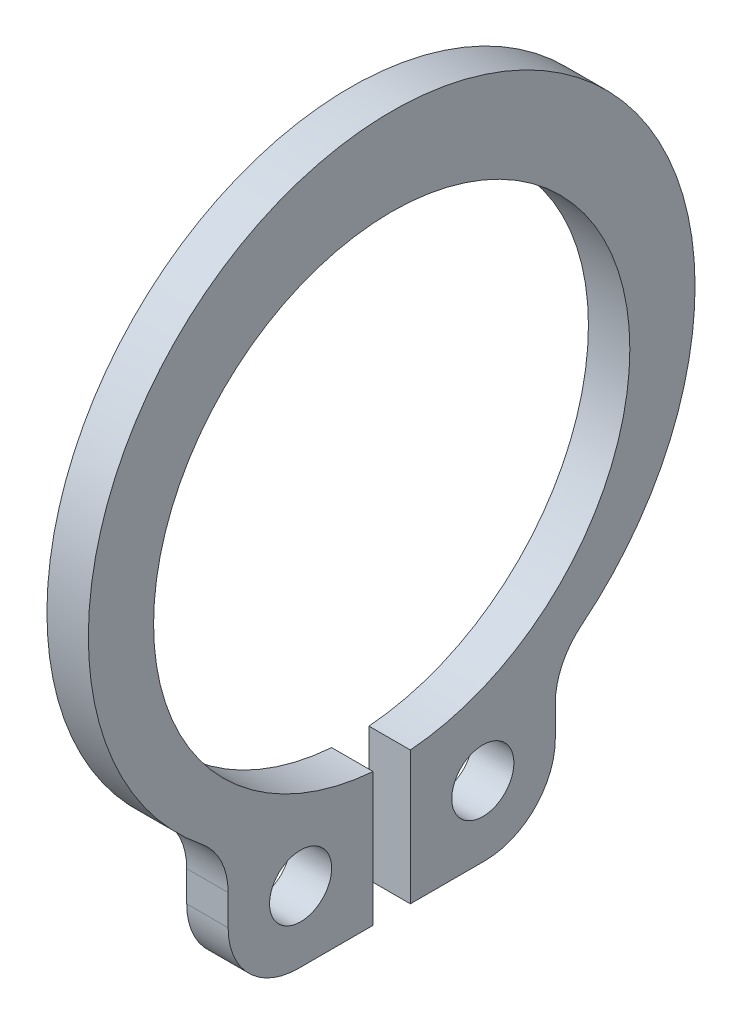
SolidWorks part; units mm, degrees
ref_plane "正面" through (0, 0, 0) normal (0, 0, 1) x (1, 0, 0)
ref_plane "平面" through (0, 0, 0) normal (0, 1, 0) x (1, 0, 0)
ref_plane "右側面" through (0, 0, 0) normal (1, 0, 0) x (0, 0, -1)
ref_plane "平面1" through (0, 0, 0) normal (1, 0, 0) x (0, 0, -1)
sketch "ｽｹｯﾁ1" plane through (0, 0, 0) normal (1, 0, 0) x (0, 0, -1)
  line L0 (-3.95, -6.5126) -> (-3.95, -7.25)
  line L1 (-2.25, -8.95) -> (-0.45, -8.95)
  line L2 (-0.45, -8.95) -> (-0.45, -5.7324)
  line L3 (0.45, -5.7324) -> (0.45, -8.95)
  line L4 (0.45, -8.95) -> (2.25, -8.95)
  line L5 (3.95, -7.25) -> (3.95, -6.5126)
  arc A0 (4.5857, -5.187) -> (-4.5857, -5.187) centre (0, 0.525) ccw
  arc A1 (-4.5857, -5.187) -> (-3.95, -6.5126) centre (-5.65, -6.5126) cw
  arc A2 (-3.95, -7.25) -> (-2.25, -8.95) centre (-2.25, -7.25) ccw
  arc A3 (-0.45, -5.7324) -> (0.45, -5.7324) centre (0, 0) cw
  arc A4 (2.25, -8.95) -> (3.95, -7.25) centre (2.25, -7.25) ccw
  arc A5 (3.95, -6.5126) -> (4.5857, -5.187) centre (5.65, -6.5126) cw
  circle A6 centre (2.2, -7.25) radius 0.75
  circle A7 centre (-2.2, -7.25) radius 0.75
extrude "ﾎﾞｽ - 押し出し1" add sketch "ｽｹｯﾁ1" against normal blind 0.5 and the other way blind 0.5
